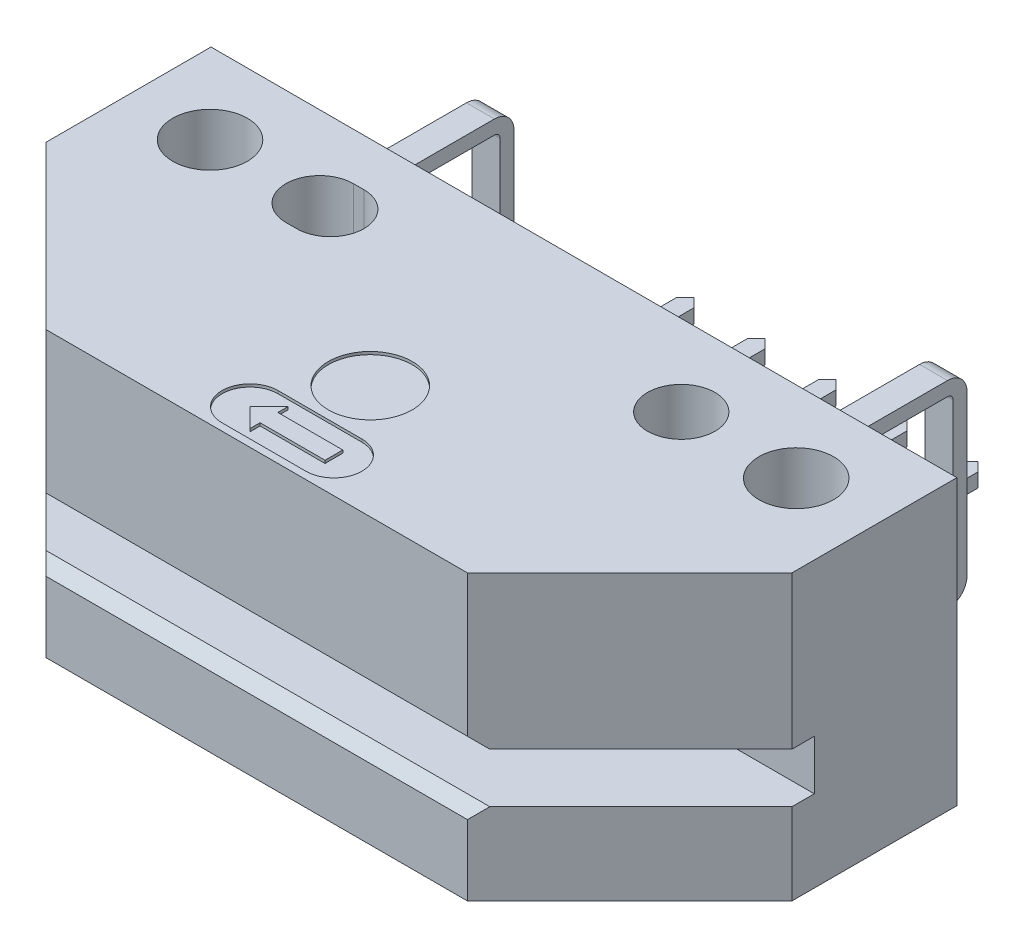
SolidWorks part; units mm, degrees
ref_plane "Front Plane" through (0, 0, 0) normal (0, 0, 1) x (1, 0, 0)
ref_plane "Top Plane" through (0, 0, 0) normal (0, 1, 0) x (1, 0, 0)
ref_plane "Right Plane" through (0, 0, 0) normal (1, 0, 0) x (0, 0, -1)
sketch "Sketch1" plane through (0, 0, 0) normal (0, 1, 0) x (1, 0, 0)
  line L0 (-13.335, 7.64) -> (13.335, 7.64)
  line L1 (13.335, 7.64) -> (13.335, 1.74)
  line L2 (13.335, 1.74) -> (7.535, -4.06)
  line L3 (7.535, -4.06) -> (-7.535, -4.06)
  line L4 (-7.535, -4.06) -> (-13.335, 1.74)
  line L5 (-13.335, 1.74) -> (-13.335, 7.64)
  line L6 (0, 0) -> (0, 7.64) construction
  line L7 (0, 0) -> (0, -4.06) construction
  line L8 (-10.48, 4.75) -> (10.48, 4.75) construction
  circle A0 centre (10.48, 4.75) radius 1.335
  circle A1 centre (-10.48, 4.75) radius 1.335
  point P14 (0, 4.75)
  dimension "D4" = 20.96
  dimension "D5" = 2.67
  dimension "D8" = 2.89
  dimension "D1" = 11.7
  dimension "D2" = 26.67
  dimension "D3" = 5.8
  dimension "D6" = 8.81
  dimension "D7" = 4.75
extrude "Boss-Extrude1" add sketch "Sketch1" along normal blind 5.46 and the other way blind 4.7
sketch "Sketch2" plane through (-13.335, 0, 0) normal (-1, 0, 0) x (0, 0, 1)
  line L0 (4.06, -4.7) -> (4.06, 5.46) construction
  line L1 (4.06, -1.78) -> (-2.54, -1.78)
  line L2 (4.06, -1.78) -> (4.06, 0)
  line L3 (4.06, 0) -> (-2.54, 0)
  line L4 (-2.54, -1.78) -> (-2.54, 0)
  line L5 (-1.74, -4.7) -> (4.06, -4.7) construction
  dimension "D1" = 2.92
  dimension "D2" = 1.78
  dimension "D3" = 2.54
extrude "Cut-Extrude1" cut sketch "Sketch2" against normal through all
chamfer "Chamfer1" distance 0.4 angle 45 2 edges at (0, -1.78, 4.06) (0, 0, 4.06)
sketch "Sketch7" plane through (0, 5.46, 0) normal (0, 1, 0) x (1, 0, 0)
  line L0 (-1.5, -2.8) -> (1.5, -2.8) construction
  line L1 (-1.5, -1.8) -> (1.5, -1.8)
  line L2 (-1.5, -3.8) -> (1.5, -3.8)
  line L3 (0, 0) -> (0, -2.8) construction
  line L4 (-1.5, -2.8) -> (-0.8226, -2.1226)
  line L5 (-0.8226, -2.1226) -> (-0.8226, -2.4822)
  line L6 (-0.8226, -2.4822) -> (1.5, -2.4822)
  line L7 (1.5, -2.4822) -> (1.5, -3.1178)
  line L8 (1.5, -3.1178) -> (-0.8226, -3.1178)
  line L9 (-0.8226, -3.1178) -> (-0.8226, -3.4774)
  line L10 (-0.8226, -3.4774) -> (-1.5, -2.8)
  circle A0 centre (0, 0) radius 1.5
  arc A1 (-1.5, -1.8) -> (-1.5, -3.8) centre (-1.5, -2.8) ccw
  arc A2 (1.5, -3.8) -> (1.5, -1.8) centre (1.5, -2.8) ccw
  point P5 (0, -2.8)
  dimension "D1" = 3
  dimension "D4" = 3
  dimension "D2" = 2.8
  dimension "D3" = 2
extrude "Cut-Extrude4" cut sketch "Sketch7" against normal blind 0.1
extrude "Cut-Extrude5" cut sketch "Sketch7<2>" along normal blind 0.1 from surface starting at face at (-10.48, -4.7, -3.415)
sketch "Sketch7<2>" plane through (0, 5.46, 0) normal (0, 1, 0) x (1, 0, 0) same geometry as "Sketch7"
sketch "Sketch3" plane through (0, 5.46, 0) normal (0, 1, 0) x (1, 0, 0)
  line L0 (10.48, 4.75) -> (-10.48, 4.75) construction
  line L1 (-6.56, 4.75) -> (-6.18, 4.75) construction
  line L2 (-6.56, 5.955) -> (-6.18, 5.955)
  line L3 (-6.56, 3.545) -> (-6.18, 3.545)
  circle A0 centre (6.37, 4.75) radius 1.205
  arc A1 (-6.56, 5.955) -> (-6.56, 3.545) centre (-6.56, 4.75) ccw
  arc A2 (-6.18, 3.545) -> (-6.18, 5.955) centre (-6.18, 4.75) ccw
  circle A3 centre (10.48, 4.75) radius 1.335 construction
  circle A5 centre (-10.48, 4.75) radius 1.335 construction
  point P8 (-6.37, 4.75)
  dimension "D1" = 4.11
  dimension "D2" = 2.41
  dimension "D4" = 2.79
  dimension "D3" = 2.41
  dimension "D5" = 4.11
extrude "Cut-Extrude2" cut sketch "Sketch3" against normal blind 2.16
sketch "Sketch4" plane through (0, -4.7, 0) normal (0, -1, 0) x (1, 0, 0)
  line L0 (8.635, -1.02) -> (-8.635, -1.02) construction
  line L1 (0, 0) -> (0, -1.02) construction
  line L2 (-8.825, -1.02) -> (-8.445, -1.02) construction
  line L3 (-8.825, 0.185) -> (-8.445, 0.185)
  line L4 (-8.825, -2.225) -> (-8.445, -2.225)
  circle A0 centre (8.635, -1.02) radius 1.205
  arc A1 (-8.825, 0.185) -> (-8.825, -2.225) centre (-8.825, -1.02) ccw
  arc A2 (-8.445, -2.225) -> (-8.445, 0.185) centre (-8.445, -1.02) ccw
  circle A3 centre (-10.48, -4.75) radius 1.335 construction
  circle A4 centre (10.48, -4.75) radius 1.335 construction
  point P8 (-8.635, -1.02)
  dimension "D2" = 2.41
  dimension "D4" = 2.79
  dimension "D5" = 3.73
  dimension "D6" = 1.845
  dimension "D1" = 17.27
  dimension "D3" = 2.41
  dimension "D7" = 1.02
extrude "Cut-Extrude3" cut sketch "Sketch4" against normal blind 2.16
sketch "Sketch5" plane through (0, -4.7, 0) normal (0, -1, 0) x (1, 0, 0)
  line L0 (-0.625, -7.64) -> (-0.625, -9.44)
  line L1 (13.335, -7.64) -> (-13.335, -7.64) construction
  line L2 (-0.625, -9.44) -> (-0.315, -9.75)
  line L3 (-0.315, -9.75) -> (-0.315, -16.335)
  line L4 (-0.315, -16.335) -> (0, -16.65)
  line L5 (0, -16.65) -> (0.315, -16.335)
  line L6 (0.315, -16.335) -> (0.315, -9.75)
  line L7 (0.315, -9.75) -> (0.625, -9.44)
  line L8 (0.625, -9.44) -> (0.625, -7.64)
  line L9 (0.625, -7.64) -> (-0.625, -7.64)
  line L10 (0, -16.65) -> (0, -7.64) construction
  line L11 (0, -7.64) -> (0, 0)
  line L12 (-7.535, 4.06) -> (7.535, 4.06) construction
  circle A0 centre (10.48, -4.75) radius 1.335 construction
  dimension "D3" = 11.9
  dimension "D1" = 0.63
  dimension "D2" = 6.9
  dimension "D4" = 45
  dimension "D5" = 1.25
  dimension "D6" = 20.71
  dimension "D7" = 2.11
extrude "Boss-Extrude2" add sketch "Sketch5" against normal blind 0.5 from offset 1.52 contours L6 L7 L8 L9 L0 L2 L3 L4 L5 offset against normal yes
pattern_linear "LPattern1" count 3 spacing 2.54 along (1, 0, 0) of "Boss-Extrude2"
pattern_linear "LPattern2" count 3 spacing 2.54 along (-1, 0, 0) of "Boss-Extrude2"
sketch "Sketch6" plane through (0, 0, 0) normal (1, 0, 0) x (0, 0, -1)
  line L0 (7.64, -3.18) -> (12.04, -3.18)
  line L1 (16.335, -3.18) -> (9.75, -3.18) construction
  line L2 (12.74, -2.48) -> (12.74, 3.2)
  line L3 (12.04, 3.9) -> (7.64, 3.9)
  line L4 (7.64, -4.7) -> (7.64, 5.46) construction
  line L5 (7.64, 3.9) -> (7.64, 3.4)
  line L6 (7.64, 3.4) -> (12.04, 3.4)
  line L7 (12.24, 3.2) -> (12.24, -2.48)
  line L8 (16.335, -2.68) -> (9.75, -2.68) construction
  line L9 (12.04, -2.68) -> (7.64, -2.68)
  line L10 (7.64, -2.68) -> (7.64, -3.18)
  line L11 (1.74, -4.7) -> (7.64, -4.7) construction
  arc A0 (12.04, -3.18) -> (12.74, -2.48) centre (12.04, -2.48) ccw
  arc A1 (12.24, -2.48) -> (12.04, -2.68) centre (12.04, -2.48) cw
  arc A2 (12.74, 3.2) -> (12.04, 3.9) centre (12.04, 3.2) ccw
  arc A3 (12.04, 3.4) -> (12.24, 3.2) centre (12.04, 3.2) cw
  point P20 (12.74, -3.18)
  point P23 (12.24, -2.68)
  dimension "D5" = 0.7
  dimension "D6" = 0.2
  dimension "D1" = 8.6
  dimension "D2" = 0.5
  dimension "D3" = 0.5
  dimension "D4" = 5.1
extrude "Boss-Extrude3" add sketch "Sketch6" along normal blind 1 from offset 7.6
extrude "Boss-Extrude4" add sketch "Sketch6<2>" against normal blind 1 from offset 7.6 offset against normal yes
sketch "Sketch6<2>" plane through (0, 0, 0) normal (1, 0, 0) x (0, 0, -1) same geometry as "Sketch6"
ref_plane "Plane1" through (0, 0, -4.75) normal (0, 0, 1) x (1, 0, 0)
